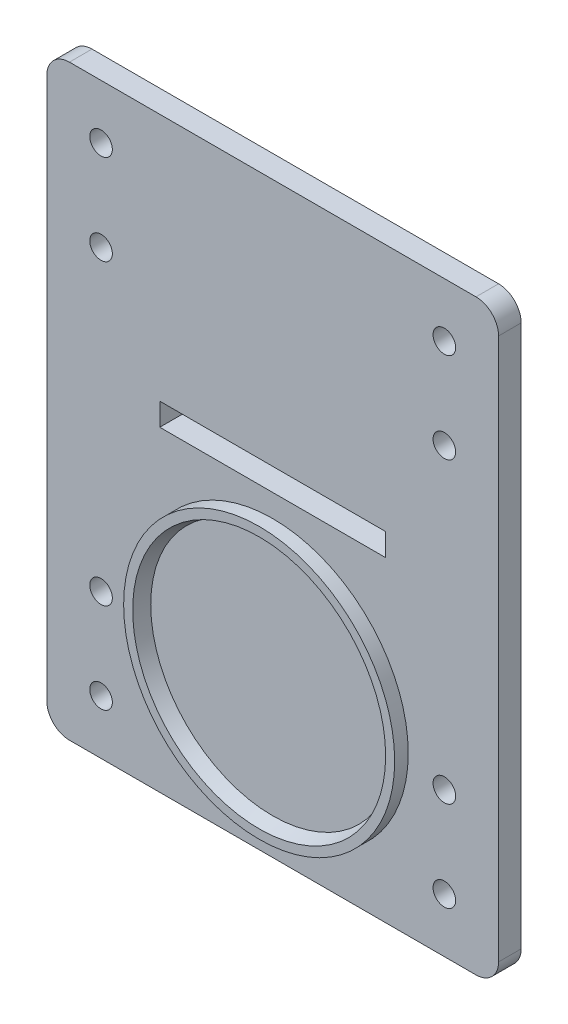
SolidWorks part; units mm, degrees
ref_plane "Ebene vorne" through (0, 0, 0) normal (0, 0, 1) x (1, 0, 0)
ref_plane "Ebene oben" through (0, 0, 0) normal (0, 1, 0) x (1, 0, 0)
ref_plane "Ebene rechts" through (0, 0, 0) normal (1, 0, 0) x (0, 0, -1)
sketch "Skizze1" plane through (0, 0, 0) normal (0, 0, 1) x (1, 0, 0)
  line L1 (-50, -65) -> (50, -65)
  line L2 (-50, -65) -> (-50, 65)
  line L3 (-50, 65) -> (50, 65)
  line L4 (50, -65) -> (50, 65)
  line L5 (-50, -65) -> (50, 65) construction
  line L6 (-50, 65) -> (50, -65) construction
  point P0 (0, 0)
  dimension "D1" = 100
  dimension "D2" = 130
extrude "Aufsatz-Linear austragen1" add sketch "Skizze1" along normal blind 5
sketch "Skizze2" plane through (0, 0, 5) normal (0, 0, 1) x (1, 0, 0)
  line L0 (-50, -65) -> (50, -65) construction
  line L1 (0, 65) -> (0, -65) construction
  line L2 (50, 65) -> (-50, 65) construction
  circle A0 centre (0, -30) radius 27
  circle A1 centre (0, -30) radius 30
  point P10 (0, 0)
  dimension "D1" = 54
  dimension "D2" = 60
  dimension "D3" = 35
extrude "Aufsatz-Linear austragen2" add sketch "Skizze2" along normal blind 3
sketch "Skizze4" plane through (0, 0, 5) normal (0, 0, 1) x (1, 0, 0)
  line L0 (-50, 65) -> (-50, -65) construction
  line L1 (-50, -65) -> (50, -65) construction
  line L2 (50, 65) -> (-50, 65) construction
  line L3 (-25, 5) -> (25, 5)
  line L4 (-25, 5) -> (-25, 10)
  line L5 (-25, 10) -> (25, 10)
  line L6 (25, 5) -> (25, 10)
  line L7 (-25, 5) -> (25, 10) construction
  line L8 (-25, 10) -> (25, 5) construction
  circle A0 centre (-38, -53) radius 2.5
  circle A1 centre (38, -53) radius 2.5
  circle A2 centre (38, 53) radius 2.5
  circle A3 centre (-38, 53) radius 2.5
  circle A4 centre (-38, -33) radius 2.5
  circle A5 centre (38, -33) radius 2.5
  circle A6 centre (38, 33) radius 2.5
  circle A7 centre (-38, 33) radius 2.5
  point P14 (0, 7.5)
  point P27 (0, 0)
  dimension "D1" = 5
  dimension "D6" = 20
  dimension "D2" = 12
  dimension "D3" = 12
  dimension "D9" = 5
  dimension "D10" = 50
  dimension "D11" = 55
  dimension "D4" = 2
  dimension "D5" = 2
  dimension "D7" = 2
  dimension "D8" = 2
extrude "Schnitt-Linear austragen1" cut sketch "Skizze4" against normal through all
chamfer "Fase1" distance 1 distance2 3 1 edges at (27, -30, 8) first distance on face at (30, -30, 8)
fillet "Verrundung1" radius 5 4 edges at (-50, -65, 2.5) (50, -65, 2.5) (50, 65, 2.5) (-50, 65, 2.5)
sketch "Skizze5" plane through (0, 0, 5) normal (0, 0, 1) x (1, 0, 0)
  line L0 (-50, 60) -> (-50, -60) construction
  line L1 (-50, 25) -> (-40, 25)
  line L2 (-50, 25) -> (-50, -25)
  line L3 (-50, -25) -> (-40, -25)
  line L4 (-40, 25) -> (-40, -25)
  line L5 (0, -4.4) -> (0, 4.4) construction
  line L6 (50, -25) -> (40, -25)
  line L7 (40, 25) -> (40, -25)
  line L8 (50, 25) -> (40, 25)
  line L9 (50, 25) -> (50, -25)
  line L10 (45, 65) -> (-45, 65) construction
  line L11 (0, 0) -> (0, -60) construction
  line L12 (-20, 25) -> (20, 25)
  line L13 (-20, 25) -> (-20, 55)
  line L14 (-20, 55) -> (20, 55)
  line L15 (20, 25) -> (20, 55)
  line L16 (-20, 25) -> (20, 55) construction
  line L17 (-20, 55) -> (20, 25) construction
  circle A0 centre (0, -30) radius 30 construction
  circle A1 centre (0, -30) radius 20
  point P14 (0, 40)
  dimension "D7" = 40
  dimension "D1" = 10
  dimension "D2" = 50
  dimension "D3" = 40
  dimension "D4" = 30
  dimension "D5" = 40
  dimension "D6" = 10
